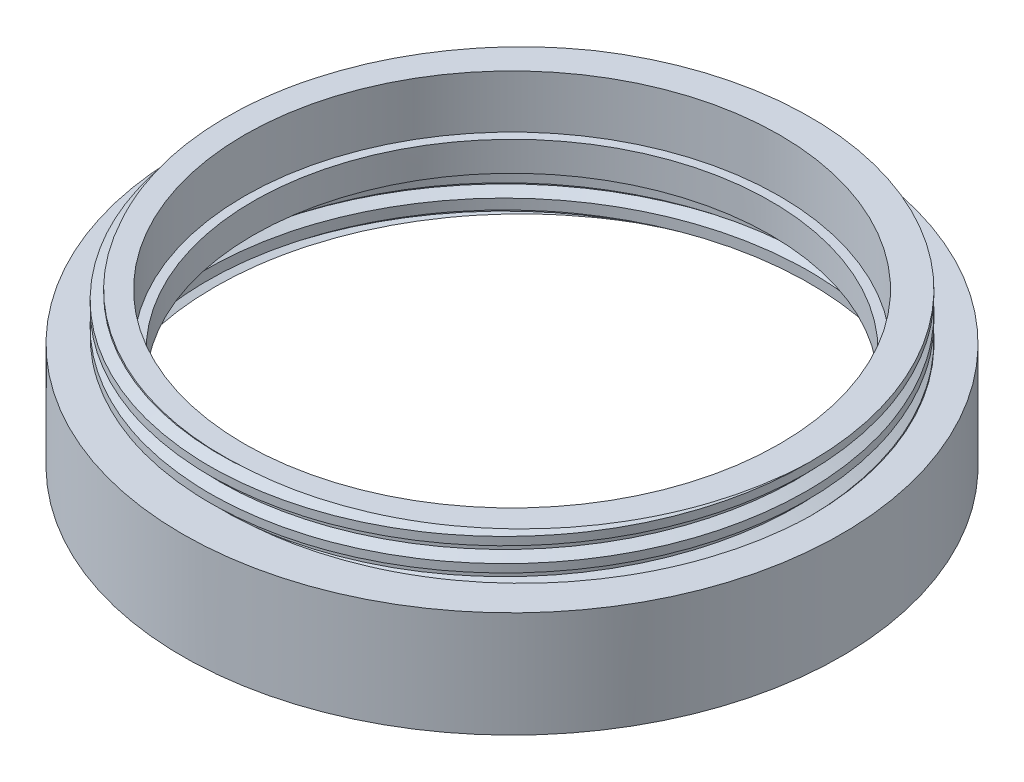
SolidWorks part; units mm, degrees
ref_plane "Front Plane" through (0, 0, 0) normal (0, 0, 1) x (1, 0, 0)
ref_plane "Top Plane" through (0, 0, 0) normal (0, 1, 0) x (1, 0, 0)
ref_plane "Right Plane" through (0, 0, 0) normal (1, 0, 0) x (0, 0, -1)
sketch "Sketch1" plane through (0, 0, 0) normal (0, 1, 0) x (1, 0, 0)
  circle A0 centre (0, 0) radius 28
  dimension "D1" = 56
extrude "Boss-Extrude1" add sketch "Sketch1" along normal blind 2
sketch "Sketch2" plane through (0, 2, 0) normal (0, 1, 0) x (1, 0, 0)
  circle A0 centre (0, 0) radius 22.74
  circle A1 centre (0, 0) radius 28
  circle A2 centre (0, 0) radius 28
  circle A3 centre (0, 0) radius 12.125
  circle M2 centre (0, 0) radius 28
  dimension "D3" = 24.25
  dimension "D1" = 0
  dimension "D2" = 5.26
extrude "Boss-Extrude2" add sketch "Sketch2" along normal blind 15 contours A0 M2 | A3
ref_plane "Plane1" through (0, 11.5, 0) normal (0, 1, 0) x (1, 0, 0)
sketch "Sketch3" [suppressed] plane through (0, 11.5, 0) normal (0, 1, 0) x (1, 0, 0)
  circle A0 centre (0, 0) radius 22.85 construction
  circle A1 centre (0, 0) radius 22.85
  circle A2 centre (0, 0) radius 22.35
  circle A5 centre (0, 0) radius 12.625
  circle A6 centre (0, 0) radius 12.625
  circle A7 centre (0, 0) radius 12.125
  circle A8 centre (0, 0) radius 12.125
  dimension "D1" = 0.5
  dimension "D2" = 0.5
  dimension "D3" = 0
sketch "Sketch4" plane through (0, 2, 0) normal (0, 1, 0) x (1, 0, 0)
  line L0 (0, 0) -> (25.2167, 0) construction
  line L2 (12.125, -2.5) -> (21.125, -2.5)
  line L3 (12.125, -2.5) -> (12.125, 2.5)
  line L4 (12.125, 2.5) -> (21.125, 2.5)
  line L5 (21.125, -2.5) -> (21.125, 2.5)
  line L6 (12.125, -2.5) -> (21.125, 2.5) construction
  line L7 (12.125, 2.5) -> (21.125, -2.5) construction
  circle A0 centre (0, 0) radius 12.125 construction
  point P3 (16.625, 0)
  dimension "D1" = 9
  dimension "D2" = 5
extrude "Cut-Extrude1" cut sketch "Sketch4" against normal through all
sketch "Sketch11" plane through (0, 17, 0) normal (0, 1, 0) x (1, 0, 0)
  circle A0 centre (0, 0) radius 25.35
  circle A1 centre (0, 0) radius 28
  circle A2 centre (0, 0) radius 28
  dimension "D1" = 0
  dimension "D2" = 2.65
extrude "Cut-Extrude2" cut sketch "Sketch11" against normal blind 5
thread "Thread3" pitch 1.5 start angle 0, offset 0, length 7, pitch 2, diameter 50.7
ref_plane "Plane4" through (-25.35, 17, 0) normal (0, 0, -1) x (-1, 0, 0)
sketch "Thread Profile3" plane through (-25.35, 17, 0) normal (0, 0, -1) x (-1, 0, 0)
  line L0 (0, 0) -> (0, 1.5) construction
  line L11 (0, 0) -> (0, 1.3125)
  line L12 (0, 1.3125) -> (-0.8119, 0.8437)
  line L13 (-0.8119, 0.8437) -> (-0.8119, 0.4687)
  line L15 (-0.8119, 0.4687) -> (0, 0)
  line L17 (-0.8119, 0.6562) -> (0, 0.6562) construction
  point P2 (0, 0)
  dimension "Pitch" = 1.5
  dimension "Profile_Angle" = 60
  dimension "Profile_Land" = 0.375
  dimension "Profile_Height" = 0.8119
sketch "Sketch14" plane through (0, 0, 0) normal (0, -1, 0) x (1, 0, 0)
  circle A1 centre (0, 0) radius 28
  circle A2 centre (0, 0) radius 28
  dimension "D1" = 0
extrude "Cut-Extrude3" cut sketch "Sketch14" against normal blind 2
sketch "Sketch15" plane through (0, 2, 0) normal (0, -1, 0) x (1, 0, 0)
  circle A0 centre (0, 0) radius 12.125 construction
  circle A1 centre (0, 0) radius 12.125
extrude "Cut-Extrude4" cut sketch "Sketch15" against normal through all
ref_plane "Plane5" through (0, 9.5, 0) normal (0, 1, 0) x (1, 0, 0)
sketch "Sketch16" plane through (0, 2, 0) normal (0, -1, 0) x (1, 0, 0)
  circle A1 centre (0, 0) radius 28 construction
  circle A2 centre (0, 0) radius 28
  circle M6 centre (0, 0) radius 22.74
  circle M7 centre (0, 0) radius 28
extrude "Cut-Extrude5" cut sketch "Sketch16" against normal blind 1 contours M7 M6
sketch "Sketch17" plane through (0, 17, 0) normal (0, 1, 0) x (1, 0, 0)
  circle A1 centre (0, 0) radius 28
  circle A2 centre (0, 0) radius 28
  dimension "D1" = 0
extrude "Cut-Extrude6" cut sketch "Sketch17" against normal blind 1
sketch "Sketch18" plane through (0, 12, 0) normal (0, 1, 0) x (1, 0, 0)
  circle A2 centre (0, 0) radius 28
  circle A3 centre (0, 0) radius 28
  circle A4 centre (0, 0) radius 22.74
  circle A5 centre (0, 0) radius 22.74
  dimension "D1" = 0
  dimension "D2" = 0
extrude "Boss-Extrude5" add sketch "Sketch18" against normal blind 3
sketch "Sketch19" plane through (0, 3, 0) normal (0, -1, 0) x (1, 0, 0)
  circle A0 centre (0, 0) radius 25.59
  circle A1 centre (0, 0) radius 22.74 construction
  circle A2 centre (0, 0) radius 22.74
  dimension "D1" = 2.85
extrude "Cut-Extrude7" cut sketch "Sketch19" against normal blind 6
thread "Thread4" pitch 1.5 profile "Thread Profile4" start angle 0, offset 0, length 6, pitch 2, diameter 51.18
ref_plane "Plane6" through (25.59, 3, 0) normal (0, 0, -1) x (1, 0, 0)
sketch "Thread Profile4" plane through (25.59, 3, 0) normal (0, 0, -1) x (1, 0, 0)
  line L0 (0, 0) -> (0, 1.5) construction
  line L1 (0, 0) -> (0.8119, 0.4687)
  line L2 (0.8119, 0.4687) -> (0.8119, 0.6562)
  line L3 (0.8119, 0.6562) -> (0, 1.125)
  line L4 (0.8119, 0.5625) -> (0, 0.5625) construction
  line L11 (0, 0) -> (0, 1.125)
  point P2 (0, 0)
  dimension "Pitch" = 1.5
  dimension "Profile_Angle" = 60
  dimension "Profile_Land" = 0.1875
  dimension "Profile_Height" = 0.8119
sketch "Sketch23" plane through (0, 16, 0) normal (0, 1, 0) x (1, 0, 0)
  circle A0 centre (0, 0) radius 22.7625
  arc A3 (-21.6638, -11.5238) -> (2.3696, -24.4234) centre (0, 0) ccw
  arc A4 (25.35, 0) -> (-14.097, 21.0688) centre (0, 0) ccw
  arc A5 (-21.6638, -11.5238) -> (2.3696, -24.4234) centre (0, 0) ccw
  arc A6 (25.35, 0) -> (-14.097, 21.0688) centre (0, 0) ccw
  spline S2 degree 3 poles (2499.9566, 1595.2091) (-233.8949, 277.2322) (-66.333, -43.2808) (7.6359, -23.4579) (8.3685, -23.2242) (9.8045, -22.6921) (10.509, -22.3933) (11.891, -21.7302) (12.5674, -21.3661) (13.8801, -20.5793) (14.5184, -20.1554) (15.7561, -19.2481) (16.3518, -18.7673) (17.4974, -17.7522) (18.0485, -17.2163) (19.0962, -16.0985) (19.5932, -15.5166) (20.5331, -14.3069) (20.9764, -13.6788) (22.2137, -11.7445) (22.922, -10.3765) (23.7874, -8.25) (24.0441, -7.5262) (24.4901, -6.0594) (24.6791, -5.3176) (39.592, 66.8111) (-255.5762, 209.5297) (-1295.1639, -2672.9448) knots -6.065192 -6.065192 -6.065192 -6.065192 0.125 0.125 0.1875 0.1875 0.25 0.25 0.3125 0.3125 0.375 0.375 0.4375 0.4375 0.5 0.5 0.5625 0.5625 0.625 0.625 0.75 0.75 0.8125 0.8125 0.875 0.875 6.821157 6.821157 6.821157 6.821157 only from (2.3696, -24.4234) to (25.35, 0)
  spline S3 degree 3 poles (-1179.3866, -2717.1551) (376.5606, -69.2786) (24.0584, 80.158) (-20.9275, 13.9396) (-21.3285, 13.2867) (-22.0669, 11.9507) (-22.4055, 11.2658) (-23.0202, 9.8638) (-23.2943, 9.1511) (-23.7766, 7.7027) (-23.9851, 6.9651) (-24.3329, 5.4769) (-24.4724, 4.7266) (-24.6824, 3.2132) (-24.7528, 2.4497) (-24.8583, 0.1619) (-24.7882, -1.3731) (-24.4709, -3.6406) (-24.3297, -4.3932) (-23.9778, -5.8815) (-23.7678, -6.6156) (-23.2796, -8.0636) (-23.0011, -8.778) (21.4702, -108.8183) (716.8128, 95.1938) (2813.0135, 951.7994) knots -6.233347 -6.233347 -6.233347 -6.233347 0.25 0.25 0.3125 0.3125 0.375 0.375 0.4375 0.4375 0.5 0.5 0.5625 0.5625 0.625 0.625 0.75 0.75 0.8125 0.8125 0.875 0.875 0.9375 0.9375 9.836585 9.836585 9.836585 9.836585 only from (-14.097, 21.0688) to (-21.6638, -11.5238)
  spline S4 degree 3 poles (2.3696, -24.4234) (3.9006, -24.3099) (5.4178, -24.0523) (7.6359, -23.4579) (8.3685, -23.2242) (9.8045, -22.6921) (10.509, -22.3933) (11.891, -21.7302) (12.5674, -21.3661) (13.8801, -20.5793) (14.5184, -20.1554) (15.7561, -19.2481) (16.3518, -18.7673) (17.4974, -17.7522) (18.0485, -17.2163) (19.0962, -16.0985) (19.5932, -15.5166) (20.5331, -14.3069) (20.9764, -13.6788) (22.2137, -11.7445) (22.922, -10.3765) (23.7874, -8.25) (24.0441, -7.5262) (24.4901, -6.0594) (24.6791, -5.3176) (25.1445, -3.0668) (25.3177, -1.5348) (25.35, 0) knots 0 0 0 0 0.125 0.125 0.1875 0.1875 0.25 0.25 0.3125 0.3125 0.375 0.375 0.4375 0.4375 0.5 0.5 0.5625 0.5625 0.625 0.625 0.75 0.75 0.8125 0.8125 0.875 0.875 1 1 1 1
  spline S5 degree 3 poles (-14.097, 21.0688) (-16.6038, 19.3102) (-18.7798, 17.1009) (-20.9275, 13.9396) (-21.3285, 13.2867) (-22.0669, 11.9507) (-22.4055, 11.2658) (-23.0202, 9.8638) (-23.2943, 9.1511) (-23.7766, 7.7027) (-23.9851, 6.9651) (-24.3329, 5.4769) (-24.4724, 4.7266) (-24.6824, 3.2132) (-24.7528, 2.4497) (-24.8583, 0.1619) (-24.7882, -1.3731) (-24.4709, -3.6406) (-24.3297, -4.3932) (-23.9778, -5.8815) (-23.7678, -6.6156) (-23.2796, -8.0636) (-23.0011, -8.778) (-22.3807, -10.1734) (-22.0385, -10.8561) (-21.6638, -11.5238) knots 0 0 0 0 0.25 0.25 0.3125 0.3125 0.375 0.375 0.4375 0.4375 0.5 0.5 0.5625 0.5625 0.625 0.625 0.75 0.75 0.8125 0.8125 0.875 0.875 0.9375 0.9375 1 1 1 1
  dimension "D1" = 45.525
  dimension "D2" = 0
ref_plane "Plane7" through (0, 11.5, 0) normal (0, 1, 0) x (1, 0, 0)
sketch "Sketch24" plane through (0, 11.5, 0) normal (0, 1, 0) x (1, 0, 0)
  circle A1 centre (0, 0) radius 22.7625 construction
  circle A2 centre (0, 0) radius 21.99
  circle A3 centre (0, 0) radius 21.99
  circle A4 centre (0, 0) radius 22.7625
  dimension "D1" = 0.75
extrude "Boss-Extrude7" add sketch "Sketch24" against normal up to surface (2.5 mm away) separate body up to face at (0, 9, -22.74)
